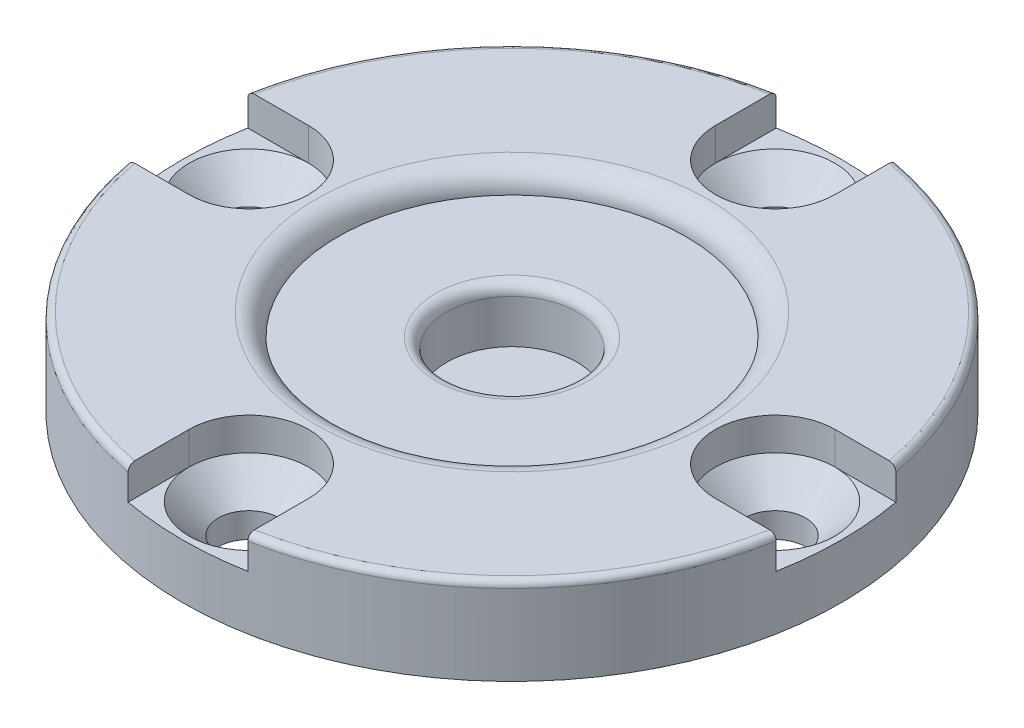
SolidWorks part; units mm, degrees
ref_plane "Front Plane" through (0, 0, 0) normal (0, 0, 1) x (1, 0, 0)
ref_plane "Top Plane" through (0, 0, 0) normal (0, 1, 0) x (1, 0, 0)
ref_plane "Right Plane" through (0, 0, 0) normal (1, 0, 0) x (0, 0, -1)
sketch "Sketch1" plane through (0, 0, 0) normal (0, 1, 0) x (1, 0, 0)
  circle A0 centre (0, 0) radius 15.15
  dimension "D1" = 30.3
extrude "Boss-Extrude1" add sketch "Sketch1" along normal blind 4
sketch "Sketch2" plane through (0, 4, 0) normal (0, 1, 0) x (1, 0, 0)
  line L0 (-2.75, 12.1) -> (-2.75, 14.8983)
  line L1 (2.75, 12.1) -> (2.75, 14.8983)
  line L2 (12.1, -2.75) -> (14.8983, -2.75)
  line L3 (12.1, 2.75) -> (14.8983, 2.75)
  line L4 (-2.75, -12.1) -> (-2.75, -14.8983)
  line L5 (2.75, -12.1) -> (2.75, -14.8983)
  line L6 (-12.1, 2.75) -> (-14.8983, 2.75)
  line L7 (-12.1, -2.75) -> (-14.8983, -2.75)
  circle A0 centre (0, 0) radius 12.1 construction
  arc A1 (-2.75, 12.1) -> (2.75, 12.1) centre (0, 12.1) ccw
  circle A2 centre (0, 0) radius 15.15 construction
  arc A3 (-2.75, 14.8983) -> (2.75, 14.8983) centre (0, 0) cw
  arc A4 (12.1, 2.75) -> (12.1, -2.75) centre (12.1, 0) ccw
  arc A5 (14.8983, 2.75) -> (14.8983, -2.75) centre (0, 0) cw
  arc A6 (2.75, -12.1) -> (-2.75, -12.1) centre (0, -12.1) ccw
  arc A7 (2.75, -14.8983) -> (-2.75, -14.8983) centre (0, 0) cw
  arc A8 (-12.1, -2.75) -> (-12.1, 2.75) centre (-12.1, 0) ccw
  arc A9 (-14.8983, -2.75) -> (-14.8983, 2.75) centre (0, 0) cw
  point P29 (0, 0)
  circle M18 centre (0, 0) radius 15.15
  dimension "D1" = 24.2
  dimension "D2" = 5.5
  dimension "D3" = 4
extrude "Cut-Extrude1" [suppressed] cut sketch "Sketch2" against normal blind 0.55
sketch "Sketch3" [suppressed] plane through (0, 1.45, 0) normal (0, 1, 0) x (1, 0, 0)
  circle A0 centre (0, 12.1) radius 1.4
  circle A1 centre (-12.1, 0) radius 1.4
  circle A2 centre (0, -12.1) radius 1.4
  circle A3 centre (12.1, 0) radius 1.4
  dimension "D1" = 2.8
extrude "Cut-Extrude2" [suppressed] cut sketch "Sketch3" against normal blind 2.55
sketch "Sketch4" plane through (0, 4, 0) normal (0, 1, 0) x (1, 0, 0)
  circle A0 centre (0, 0) radius 8
  dimension "D1" = 16
extrude "Cut-Extrude3" cut sketch "Sketch4" against normal blind 1
sketch "Sketch5" plane through (0, 3, 0) normal (0, 1, 0) x (1, 0, 0)
  circle A0 centre (0, 0) radius 3
  dimension "D1" = 6
extrude "Cut-Extrude4" cut sketch "Sketch5" against normal blind 2.5
fillet "Fillet1" radius 1 1 edges at (0, 4, 8)
fillet "Fillet2" radius 0.5 1 edges at (0, 3, 3)
fillet "Fillet3" radius 0.3 1 edges at (0, 4, 15.15)
extrude "Cut-Extrude5" cut sketch "Sketch2<2>" against normal blind 1.5 contours L7 A8 L6 M18 | L5 A6 L4 M18 | L3 A4 L2 M18 | A1 L1 A3 L0 region at (-12.4671, 4, 0) region at (12.4671, 4, 0) region at (0, 4, 12.4671)
sketch "Sketch2<2>" plane through (0, 4, 0) normal (0, 1, 0) x (1, 0, 0) same geometry as "Sketch2"
hole_wizard "CSK for M2.5 Flat Head Machine Screw1" positions "Sketch6" profile "Sketch7" countersink size "M2.5" standard "ANSI Metric" end condition through all
sketch "Sketch6" plane through (0, 2.5, 0) normal (0, 1, 0) x (1, 0, 0)
  point P0 (0, 12.1)
  point P3 (-12.1, 0)
  point P6 (12.1, 0)
  point P9 (0, -12.1)
sketch "Sketch7" plane through (0, 2.5, -12.1) normal (1, 0, 0) x (0, 0, 1)
  line L0 (0, 0) -> (0, 2.5)
  line L1 (0, 2.5) -> (1.4, 2.5)
  line L2 (1.4, 2.5) -> (1.4, 1.35)
  line L3 (1.4, 1.35) -> (2.75, 0)
  line L5 (2.75, 0) -> (0, 0)
  line L6 (-1.4, 1.35) -> (-2.75, 0) construction
  line L11 (0, -6.35) -> (0, 107.95) construction
  dimension "Thru Hole Dia." = 2.8
  dimension "Thru Hole Depth" = 2.5
  dimension "Near C'Sink Dia." = 5.5
  dimension "Near C'Sink Angle" = 90
